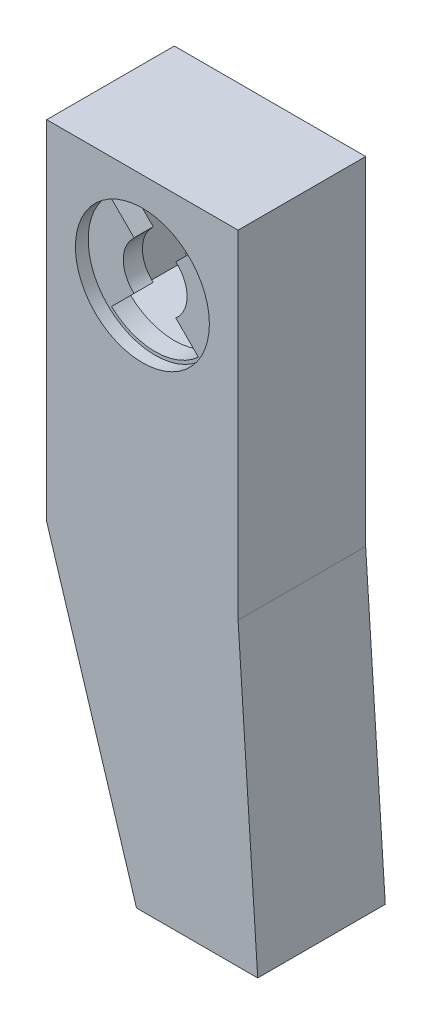
SolidWorks part; units mm, degrees
ref_plane "Front Plane" through (0, 0, 0) normal (0, 0, 1) x (1, 0, 0)
ref_plane "Top Plane" through (0, 0, 0) normal (0, 1, 0) x (1, 0, 0)
ref_plane "Right Plane" through (0, 0, 0) normal (1, 0, 0) x (0, 0, -1)
sketch "Sketch1" plane through (0, 0, 0) normal (0, 0, 1) x (1, 0, 0)
  line L7 (-161.4407, 28.0286) -> (-187.8407, 1.6286) construction
  line L14 (-175.5642, -70.1714) -> (-156.5642, -70.1714)
  line L15 (-159.6407, -23.1318) -> (-156.5642, -70.1714)
  line L21 (-189.6407, -24.7701) -> (-175.5642, -70.1714)
  line L26 (-161.4407, 1.6286) -> (-187.8407, 28.0286) construction
  line L28 (-189.6407, -1.8875) -> (-189.6407, -24.7701)
  line L32 (-171.4033, 11.0182) -> (-167.8619, 7.4769)
  line L33 (-177.9493, 11.0798) -> (-181.4882, 7.5408)
  line L34 (-171.4033, 18.6389) -> (-167.8619, 22.1803)
  line L35 (-177.9493, 18.6389) -> (-181.4564, 22.1461)
  line L36 (-187.8407, 28.0286) -> (-187.8407, 1.6286)
  line L37 (-161.4407, 28.0286) -> (-161.4407, 1.6286)
  line L38 (-161.4407, 1.6286) -> (-187.8407, 1.6286)
  line L39 (-161.4407, 28.0286) -> (-187.8407, 28.0286)
  line L40 (-159.6407, -1.8875) -> (-159.6407, -23.1318)
  line L42 (-189.6407, 29.8286) -> (-159.6407, 29.8286)
  line L43 (-189.6407, -1.8875) -> (-189.6407, 29.8286)
  line L44 (-159.6407, -1.8875) -> (-189.6407, -1.8875)
  line L45 (-159.6407, 29.8286) -> (-159.6407, -1.8875)
  line L46 (-178.1762, 18.3641) -> (-177.9493, 18.6389)
  arc A6 (-177.9493, 11.0798) -> (-178.1762, 18.3641) centre (-174.6407, 14.8286) cw
  arc A7 (-181.4564, 22.1461) -> (-167.8619, 22.1803) centre (-174.6407, 14.8286) cw
  arc A8 (-171.4033, 18.6389) -> (-171.4033, 11.0182) centre (-174.6407, 14.8286) cw
  arc A9 (-167.8619, 7.4769) -> (-181.4882, 7.5408) centre (-174.6407, 14.8286) cw
  circle A10 centre (-174.6407, 14.8286) radius 10.5
  dimension "D2" = 19
  dimension "D15" = 22.8825
extrude "Boss-Extrude3" add sketch "Sketch1<3>" against normal blind 20 separate body contours L44 | L40 L44 | L45 L42 L43 L44 L39 L37 L38 L36 region at (-172.1684, -33.3992, 0) region at (-189.2041, 13.9705, 0)
sketch "Sketch1<3>" plane through (0, 0, 0) normal (0, 0, 1) x (1, 0, 0) same geometry as "Sketch1"
extrude "Boss-Extrude7" add sketch "Sketch1<10>" against normal blind 5 contours L37 L39 L36 L38 A10 | A10 L32 A9 L33 A6 L46 L35 A7 L34 A8 region at (-174.6407, 27.6552, 0) region at (-184.8437, 14.8286, 0)
sketch "Sketch1<10>" plane through (0, 0, 0) normal (0, 0, 1) x (1, 0, 0) same geometry as "Sketch1"
extrude "Cut-Extrude1" cut sketch "Sketch1" against normal blind 2 contours A10 L32 A9 L33 A6 L46 L35 A7 L34 A8 region at (-184.8437, 14.8286, 0)
ref_plane "Plane1" through (0, 0, 0) normal (0, 0, 1) x (1, 0, 0)
ref_plane "Plane2" through (0, -70.1714, 0) normal (0, -1, 0) x (-1, 0, 0)
sketch "Sketch2" plane through (0, -70.1714, 0) normal (0, -1, 0) x (-1, 0, 0)
  line L0 (175.5642, 20) -> (175.5642, 0) construction
  line L1 (175.5642, 20) -> (156.5642, 20) construction
  circle A0 centre (161.5642, 12) radius 1.4
  circle A1 centre (170.5642, 12) radius 1.4
  dimension "D1" = 2.8
  dimension "D2" = 2.8
  dimension "D3" = 9
  dimension "D4" = 5
  dimension "D6" = 8
extrude "Cut-Extrude2" cut sketch "Sketch2" against normal blind 15
